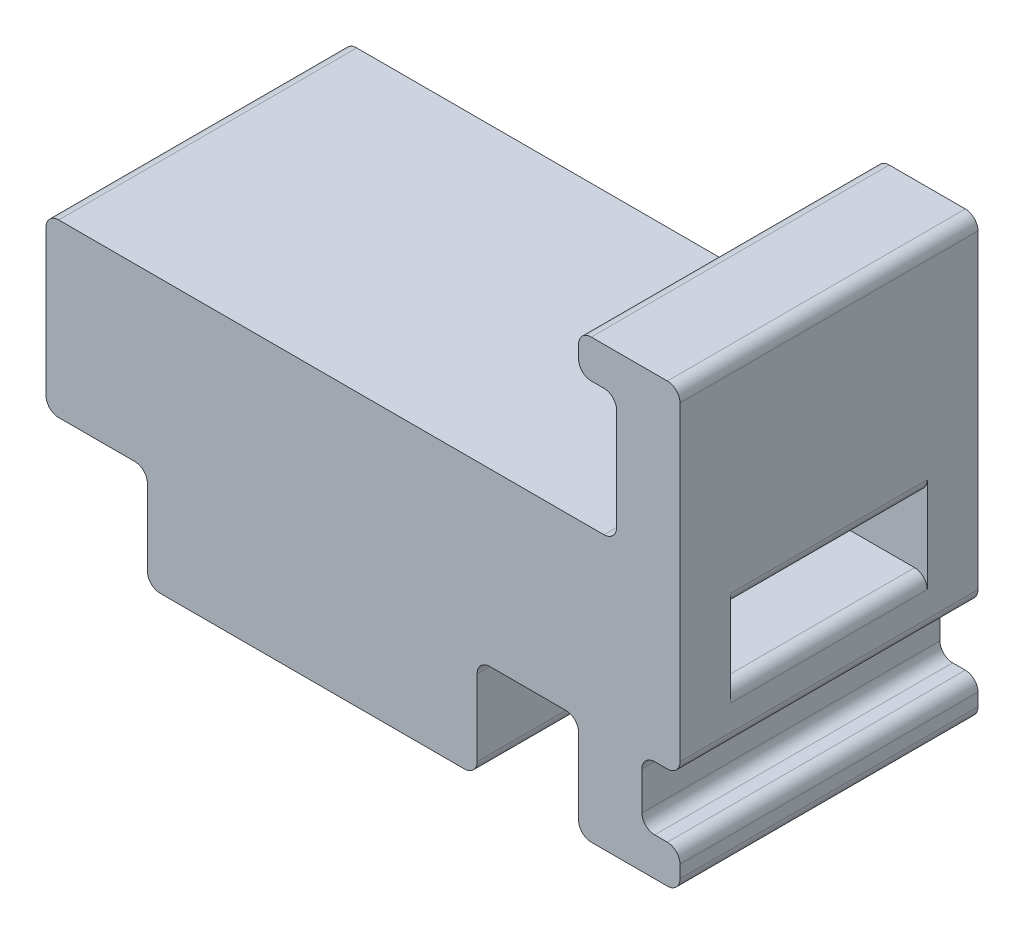
SolidWorks part; units mm, degrees
ref_plane "Front Plane" through (0, 0, 0) normal (0, 0, 1) x (1, 0, 0)
ref_plane "Top Plane" through (0, 0, 0) normal (0, 1, 0) x (1, 0, 0)
ref_plane "Right Plane" through (0, 0, 0) normal (1, 0, 0) x (0, 0, -1)
sketch "Sketch1" plane through (0, 0, 0) normal (0, 0, 1) x (1, 0, 0)
  line L2 (-25, 6.5) -> (-25, -5)
  line L4 (25, 8.5) -> (25, -5)
  line L5 (17, -7) -> (17, -11)
  line L6 (17, -11) -> (17, -13)
  line L7 (25, 16) -> (25, 8.5)
  line L13 (18, 20.5) -> (24, 20.5)
  line L14 (25, 19.5) -> (25, 16)
  line L15 (17, 19.5) -> (17, 18.5)
  line L16 (18, 17.5) -> (19, 17.5)
  line L17 (20, 16.5) -> (20, 8.5)
  line L18 (-24, 7.5) -> (19, 7.5)
  line L19 (18, -14) -> (24, -14)
  line L20 (25, -13) -> (25, -12)
  line L21 (24, -11) -> (23, -11)
  line L22 (22, -10) -> (22, -7)
  line L24 (23, -6) -> (24, -6)
  line L25 (-24, -6) -> (-18, -6)
  line L26 (-4, -14) -> (-16, -14)
  line L27 (-4, -14) -> (8, -14)
  line L28 (9, -13) -> (9, -7)
  line L29 (-17, -13) -> (-17, -7)
  line L30 (10, -6) -> (16, -6)
  line L31 (-25, 0.75) -> (-27.8717, 0.75) construction
  line L32 (-27.8717, 0.75) -> (-27.8717, 7.5) construction
  line L33 (-27.8717, 0.75) -> (-29.26, 0.75)
  line L34 (-29.26, 0.75) -> (-29.26, 3.5)
  line L35 (-29.26, 3.5) -> (-29.26, 7.5) construction
  arc A1 (25, 19.5) -> (24, 20.5) centre (24, 19.5) ccw
  arc A2 (17, 19.5) -> (18, 20.5) centre (18, 19.5) cw
  arc A3 (18, 17.5) -> (17, 18.5) centre (18, 18.5) cw
  arc A4 (20, 16.5) -> (19, 17.5) centre (19, 16.5) ccw
  arc A5 (20, 8.5) -> (19, 7.5) centre (19, 8.5) cw
  arc A6 (25, -5) -> (24, -6) centre (24, -5) cw
  arc A7 (23, -6) -> (22, -7) centre (23, -7) ccw
  arc A8 (23, -11) -> (22, -10) centre (23, -10) cw
  arc A9 (25, -12) -> (24, -11) centre (24, -12) ccw
  arc A10 (25, -13) -> (24, -14) centre (24, -13) cw
  arc A11 (18, -14) -> (17, -13) centre (18, -13) cw
  arc A12 (17, -7) -> (16, -6) centre (16, -7) ccw
  arc A13 (-25, -5) -> (-24, -6) centre (-24, -5) ccw
  arc A14 (-25, 6.5) -> (-24, 7.5) centre (-24, 6.5) cw
  arc A15 (9, -7) -> (10, -6) centre (10, -7) cw
  arc A16 (9, -13) -> (8, -14) centre (8, -13) cw
  arc A17 (-16, -14) -> (-17, -13) centre (-16, -13) cw
  arc A18 (-17, -7) -> (-18, -6) centre (-18, -7) ccw
  point P0 (0, 0)
  point P25 (17, 17.5)
  dimension "D1" = 1
extrude "Boss-Extrude2" add sketch "Sketch1" along normal mid plane 23.5 contours L18 A5 L17 A4 L16 A3 L15 A2 L13 A1 L14 L7 L4 A6 L24 A7 L22 A8 L21 A9 L20 A10 L19 A11 L6 L5 A12 L30 A15 L28 A16 L27 L26 A17 L29 A18 L25 A13 L2 A14
sketch "Sketch5" plane through (-25, 0, 0) normal (-1, 0, 0) x (0, 0, 1)
  line L2 (-7.75, 3.5) -> (7.75, 3.5)
  line L3 (-7.75, 3.5) -> (-7.75, -2)
  line L4 (-7.75, -2) -> (7.75, -2)
  line L5 (7.75, 3.5) -> (7.75, -2)
  point P4 (0, 0.75)
extrude "Cut-Extrude2" cut sketch "Sketch5" against normal through all contours L2 L5 L4 L3
fillet "Fillet1" radius 1 4 edges at (25, -2, 0) (25, 3.5, 0) (-25, -2, 0) (-25, 3.5, 0)
sketch "Sketch7" plane through (0, -14, 0) normal (0, -1, 0) x (1, 0, 0)
  line L0 (-4, 7.5) -> (-4, 5.5) construction
  line L1 (-9.099, 5.5) -> (1.099, 5.5)
  arc A1 (1.099, 5.5) -> (-9.099, 5.5) centre (-4, 0) cw
extrude "Cut-Extrude3" cut sketch "Sketch7" against normal blind 10
ref_plane "SnapFeature-Plane" through (0, -7.75, 0) normal (0, 1, 0) x (1, 0, 0)
sketch "Sketch8" plane through (0, -7.75, 0) normal (0, 1, 0) x (1, 0, 0)
  line L0 (-4, -5.5) -> (-4, -6.5) construction
  line L1 (1.099, -5.5) -> (-9.099, -5.5) construction
  line L2 (1.4772, -6.5) -> (-9.4772, -6.5)
  arc A1 (1.4772, -6.5) -> (-9.4772, -6.5) centre (-4, 0) ccw
extrude "Cut-Extrude4" cut sketch "Sketch8" against normal mid plane 2 contours L2 A1
